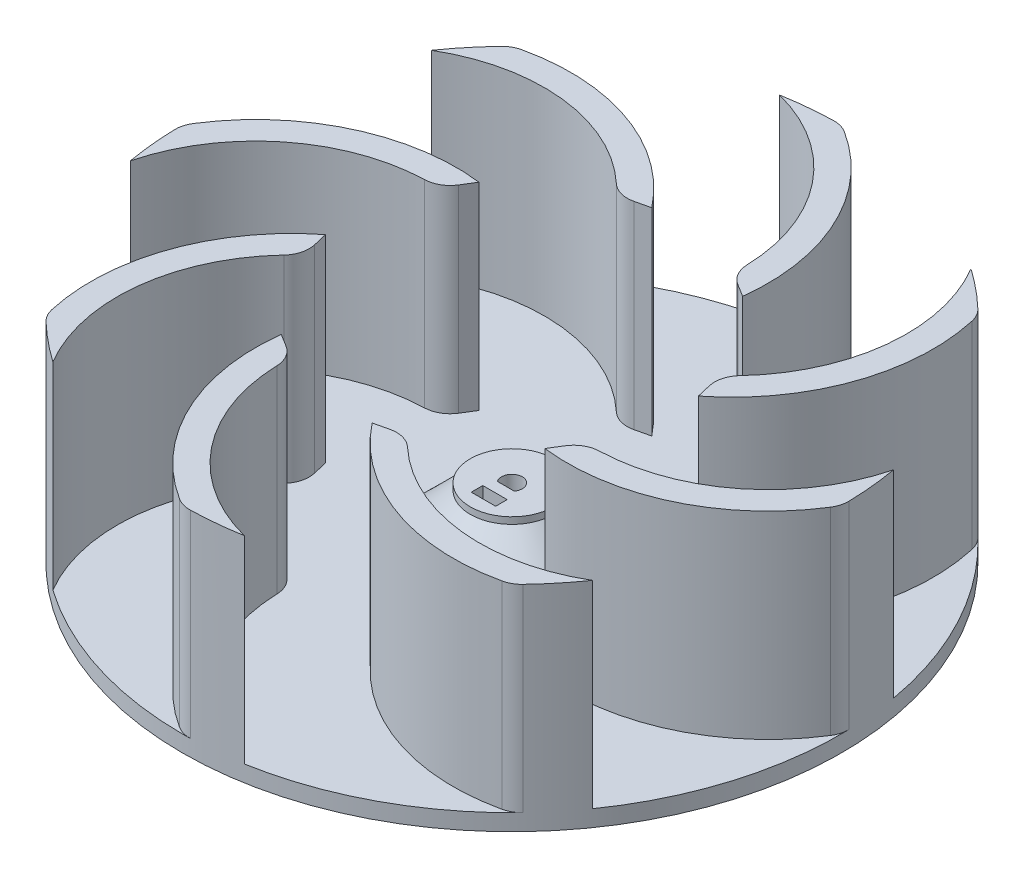
SolidWorks part; units mm, degrees
ref_plane "Front Plane" through (0, 0, 0) normal (0, 0, 1) x (1, 0, 0)
ref_plane "Top Plane" through (0, 0, 0) normal (0, 1, 0) x (1, 0, 0)
ref_plane "Right Plane" through (0, 0, 0) normal (1, 0, 0) x (0, 0, -1)
sketch "Sketch1" plane through (0, 0, 0) normal (0, 1, 0) x (1, 0, 0)
  line L0 (-2.5495, -1.85) -> (2.5495, -1.85)
  line L1 (0, -3.15) -> (0, -12.65) construction
  line L3 (-3.7, -5.15) -> (3.7, -5.15)
  line L4 (-3.7, -5.15) -> (-3.7, -8.65)
  line L5 (-3.7, -8.65) -> (3.7, -8.65)
  line L6 (3.7, -5.15) -> (3.7, -8.65)
  line L7 (-3.7, -5.15) -> (3.7, -8.65) construction
  line L8 (-3.7, -8.65) -> (3.7, -5.15) construction
  circle A0 centre (0, 0) radius 100
  circle A1 centre (0, 0) radius 3.15
  circle A2 centre (0, 0) radius 12.65
  point P7 (0, 3.15)
  point P10 (0, -6.9)
  point P15 (0, 0)
  dimension "D1" = 6.3
  dimension "D7" = 200
  dimension "D2" = 5
  dimension "D3" = 7.4
  dimension "D4" = 3.5
  dimension "D5" = 2
  dimension "D6" = 4
extrude "Boss-Extrude1" add sketch "Sketch1" against normal blind 5 contours A0 A2 | A2 L3 L6 L5 L4 A1 | L6 L3 L4 L5 | L0 A1 region at (0, 0, 2.3805) region at (0, 0, 6.9) region at (-97.1716, 0, 0) region at (-12.2922, 0, 0)
extrude "Boss-Extrude2" add sketch "Sketch1<3>" along normal blind 16 contours A2 L3 L6 L5 L4 A1 | L0 A1 region at (0, 0, 2.3805) region at (-12.2922, 0, 0)
sketch "Sketch1<3>" plane through (0, 0, 0) normal (0, 1, 0) x (1, 0, 0) same geometry as "Sketch1"
sketch "Sketch3" plane through (0, 0, 5.15) normal (0, 0, 1) x (1, 0, 0)
  line L0 (0, 16) -> (0, 0) construction
  line L4 (-3.7, 0) -> (3.7, 0)
  line L5 (3.7, 0) -> (3.7, 16)
  line L6 (3.7, 16) -> (-3.7, 16)
  line L7 (-3.7, 16) -> (-3.7, 0)
  line L8 (-3.7, 0) -> (3.7, 0) construction
  line L9 (3.7, 0) -> (3.7, 16) construction
  line L10 (3.7, 16) -> (-3.7, 16) construction
  line L11 (-3.7, 16) -> (-3.7, 0) construction
  circle A0 centre (0, 8) radius 2
  dimension "D2" = 4
  dimension "D1" = 0
chamfer "Chamfer1" distance 14 angle 45 1 edges at (0, 0, 12.65)
extrude "Cut-Extrude1" cut sketch "Sketch3" along normal through all and the other way up to vertex (5.15 mm away) contours A0 other way up to point (0, 0, 0)
fillet "Fillet1" radius 3 2 edges at (3.7, 0, 6.9) (-3.7, 0, 6.9)
sketch "Sketch4" plane through (0, 0, 0) normal (0, 1, 0) x (1, 0, 0)
  line L0 (0, 0) -> (0, -100) construction
  line L1 (0, -100) -> (-86.6025, -50) construction
  line L2 (0, 0) -> (-60, -80) construction
  line L3 (-30, -40) -> (-13.2388, 99.1198) construction
  line L4 (-22.3747, -44.7143) -> (-30, -40)
  circle A0 centre (0, 0) radius 100 construction
  arc A1 (0, -100) -> (-30, -40) centre (30.4371, -47.2815) cw
  circle A2 centre (0, 0) radius 50 construction
  arc A3 (17.2875, -98.4944) -> (-22.3747, -44.7143) centre (30.4371, -47.2815) cw
  arc A4 (17.2875, -98.4944) -> (0, -100) centre (0, 0) cw
  point P13 (-19.5991, -51.3894)
  point P14 (0, 0)
  dimension "D3" = 100
  dimension "D4" = 8
  dimension "D1" = 60
  dimension "D2" = 30
extrude "Boss-Extrude3" add sketch "Sketch4" along normal blind 60
fillet "Fillet3" radius 8 1 edges at (-22.3747, 30, 44.7143)
fillet "Fillet4" radius 8 1 edges at (0, 30, 100)
sketch "Sketch5" plane through (0, 0, 0) normal (1, 0, 0) x (0, 0, -1)
  line L0 (0, 0) -> (0, 64.7284) construction
pattern_circular "CirPattern1" count 8 over 360 about axis through (0, 0, 0) along (0, 1, 0) of "Boss-Extrude3", "Fillet3", "Fillet4" reverse direction yes
